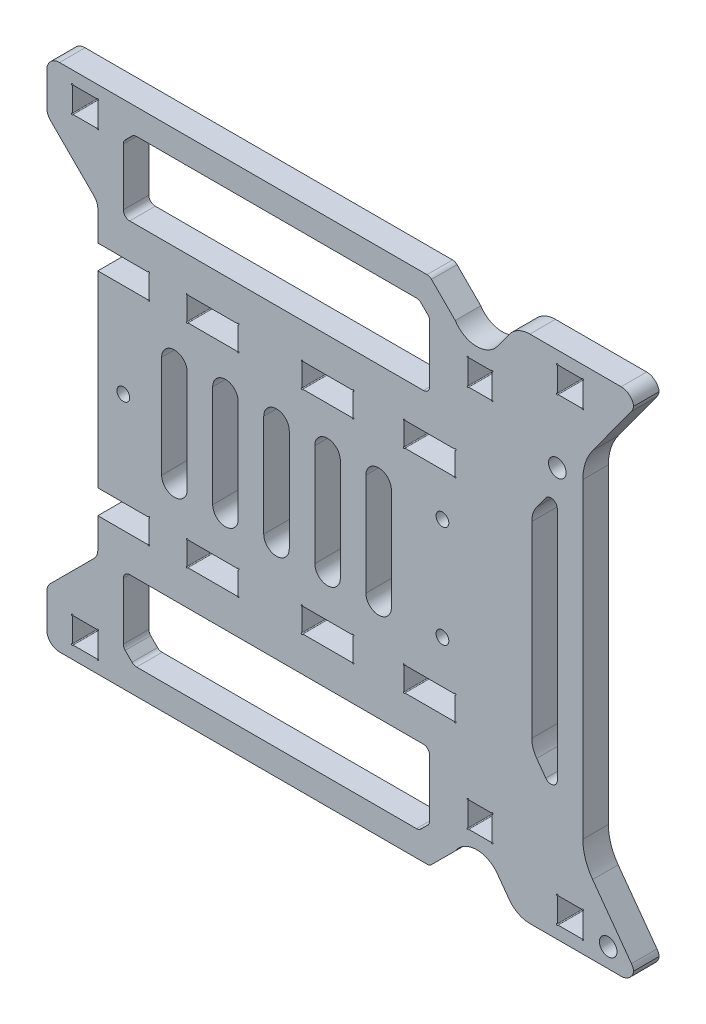
SolidWorks part; units mm, degrees
ref_plane "Front Plane" through (0, 0, 0) normal (0, 0, 1) x (1, 0, 0)
ref_plane "Top Plane" through (0, 0, 0) normal (0, 1, 0) x (1, 0, 0)
ref_plane "Right Plane" through (0, 0, 0) normal (1, 0, 0) x (0, 0, -1)
sketch "Sketch1" plane through (0, 0, 0) normal (0, 0, 1) x (1, 0, 0)
  line L0 (83.672, 0) -> (-43.8164, 0) construction
  line L1 (10.525, 38.1) -> (10.525, -38.1) construction
  line L2 (-27.575, 38.1) -> (48.625, 38.1)
  line L3 (99.425, -63.5) -> (99.425, -60.325)
  line L4 (99.425, -60.325) -> (74.025, -25.4)
  line L5 (-27.575, -63.5) -> (48.625, -63.5)
  line L6 (-27.575, 38.1) -> (-27.575, 54.5197)
  line L7 (48.625, 38.1) -> (48.625, 54.5197)
  line L8 (-24.9447, 57.15) -> (45.9947, 57.15)
  line L9 (-27.575, 63.5) -> (48.625, 63.5)
  line L10 (-33.925, 57.15) -> (-33.925, -57.15)
  line L11 (-27.575, 63.5) -> (-33.925, 57.15)
  line L12 (-24.9447, 57.15) -> (-27.575, 54.5197)
  line L13 (99.425, 63.5) -> (99.425, 60.325)
  line L14 (-23.0849, 59.0099) -> (-29.4349, 52.6599) construction
  line L15 (99.425, 60.325) -> (74.025, 25.4)
  line L16 (74.025, 25.4) -> (74.025, -25.4)
  line L17 (48.625, -38.1) -> (48.625, -54.5197)
  line L18 (-27.575, -38.1) -> (48.625, -38.1)
  line L19 (-24.9447, -57.15) -> (45.9947, -57.15)
  line L20 (-24.9447, -57.15) -> (-27.575, -54.5197)
  line L21 (-27.575, -38.1) -> (-27.575, -54.5197)
  line L22 (-27.575, -63.5) -> (-33.925, -57.15)
  line L23 (48.625, -63.5) -> (54.975, -57.15)
  line L24 (48.625, 63.5) -> (54.975, 57.15)
  line L25 (70.3271, -63.5) -> (99.425, -63.5)
  line L26 (45.9947, 57.15) -> (48.625, 54.5197)
  line L27 (45.9947, -57.15) -> (48.625, -54.5197)
  line L28 (70.3271, 63.5) -> (65.7089, 57.15)
  line L29 (70.3271, 63.5) -> (99.425, 63.5)
  line L30 (78.8831, 75.2646) -> (53.4831, 40.3396) construction
  line L31 (54.975, -42.3909) -> (54.975, -57.15)
  line L32 (70.3271, -63.5) -> (65.7089, -57.15)
  line L34 (48.625, -63.5) -> (54.975, -57.15)
  line L35 (65.7089, 57.15) -> (54.975, 42.3909)
  line L36 (54.975, 42.3909) -> (54.975, 57.15)
  line L37 (65.7089, -57.15) -> (54.975, -42.3909)
  point P7 (-27.575, 0)
  point P21 (74.025, 0)
  point P22 (-33.925, 0)
  dimension "D1" = 25.4
  dimension "D2" = 76.2
  dimension "D3" = 127
  dimension "D4" = 6.35
  dimension "D7" = 3.175
  dimension "D8" = 25.4
  dimension "D9" = 25.4
  dimension "D6" = 6.35
extrude "Boss-Extrude1" add sketch "Sketch1" along normal blind 6.35 contours L23 L32 L25 L3 L4 L16 L15 L13 L29 L28 L24 L9 L11 L10 L22 L5 L8 L26 L7 L2 L6 L12 L27 L19 L20 L21 L18 L17 region at (27.1557, 0, 0)
fillet "Fillet1" radius 6.35 4 edges at (70.3271, 63.5, 3.175) (70.3271, -63.5, 3.175) (54.975, -42.3909, 3.175) (54.975, 42.3909, 3.175)
fillet "Fillet3" radius 3.175 4 edges at (99.425, 63.5, 3.175) (99.425, 60.325, 3.175) (99.425, -60.325, 3.175) (99.425, -63.5, 3.175)
fillet "Fillet4" radius 6.35 2 edges at (74.025, -25.4, 3.175) (74.025, 25.4, 3.175)
fillet "Fillet7" radius 1.5875 4 edges at (-27.575, -38.1, 3.175) (48.625, -38.1, 3.175) (48.625, 38.1, 3.175) (-27.575, 38.1, 3.175)
fillet "Fillet8" radius 1.5875 2 edges at (48.625, -63.5, 3.175) (48.625, 63.5, 3.175)
fillet "Fillet9" radius 1.5875 8 edges at (-27.575, 54.5197, 3.175) (-24.9447, 57.15, 3.175) (-27.575, -54.5197, 3.175) (-24.9447, -57.15, 3.175) (45.9947, -57.15, 3.175) (48.625, -54.5197, 3.175) (48.625, 54.5197, 3.175) (45.9947, 57.15, 3.175)
sketch "Sketch2" plane through (0, 0, 6.35) normal (0, 0, 1) x (1, 0, 0)
  line L0 (-33.925, 0) -> (74.025, 0) construction
  line L1 (-33.925, 57.15) -> (-33.925, -57.15) construction
  line L2 (74.025, 23.3351) -> (74.025, -23.3351) construction
  line L3 (48.625, 39.6875) -> (48.625, 53.8622) construction
  line L4 (58.3484, 50.8) -> (63.9714, 50.8)
  line L5 (58.15, 50.6016) -> (58.15, 44.6484)
  line L6 (58.3484, 44.45) -> (63.9714, 44.45)
  line L7 (64.1698, 50.6016) -> (64.1698, 44.6484)
  line L8 (64.1698, -50.6016) -> (64.1698, -44.6484)
  line L9 (58.3484, -50.8) -> (63.9714, -50.8)
  line L10 (58.15, -50.6016) -> (58.15, -44.6484)
  line L11 (58.3484, -44.45) -> (63.9714, -44.45)
  arc A0 (58.3484, 50.8) -> (58.15, 50.6016) centre (58.15, 50.8) ccw
  arc A1 (64.1698, 50.6016) -> (63.9714, 50.8) centre (64.1698, 50.8) ccw
  arc A2 (63.9714, 44.45) -> (64.1698, 44.6484) centre (64.1698, 44.45) ccw
  arc A3 (58.15, 44.6484) -> (58.3484, 44.45) centre (58.15, 44.45) ccw
  arc A4 (63.9714, -44.45) -> (64.1698, -44.6484) centre (64.1698, -44.45) cw
  arc A5 (64.1698, -50.6016) -> (63.9714, -50.8) centre (64.1698, -50.8) cw
  arc A6 (58.3484, -50.8) -> (58.15, -50.6016) centre (58.15, -50.8) cw
  arc A7 (58.15, -44.6484) -> (58.3484, -44.45) centre (58.15, -44.45) cw
  point P10 (48.625, 46.7748)
  dimension "D5" = 0.3969
  dimension "D6" = 0.3969
  dimension "D7" = 0.3969
  dimension "D8" = 0.3969
  dimension "D1" = 6.0198
  dimension "D2" = 6.35
  dimension "D3" = 50.8
  dimension "D4" = 9.525
extrude "Cut-Extrude1" cut sketch "Sketch2" against normal through all
sketch "Sketch5" plane through (0, 0, 6.35) normal (0, 0, 1) x (1, 0, 0)
  line L0 (-33.925, 29.3675) -> (74.025, 29.3675) construction
  line L1 (-33.925, 57.15) -> (-33.925, -57.15) construction
  line L2 (74.025, 23.3351) -> (74.025, -23.3351) construction
  line L3 (-25.9875, 38.1) -> (47.0375, 38.1) construction
  line L4 (-33.925, 23.3731) -> (74.025, 23.3731) construction
  line L5 (-33.925, 0) -> (74.025, 0) construction
  line L6 (-11.5016, 29.3675) -> (0.8016, 29.3675)
  line L7 (-11.7, 29.169) -> (-11.7, 23.5715)
  line L8 (-11.5016, 23.3731) -> (0.8016, 23.3731)
  line L9 (1, 29.169) -> (1, 23.5715)
  line L10 (42.4734, 29.3675) -> (54.7766, 29.3675)
  line L11 (42.275, 29.169) -> (42.275, 23.5715)
  line L12 (42.4734, 23.3731) -> (54.7766, 23.3731)
  line L13 (54.975, 29.169) -> (54.975, 23.5715)
  line L14 (29.3766, 29.3675) -> (17.0734, 29.3675)
  line L15 (29.575, 29.169) -> (29.575, 23.5715)
  line L16 (29.3766, 23.3731) -> (17.0734, 23.3731)
  line L17 (16.875, 29.169) -> (16.875, 23.5715)
  line L18 (-21.4234, 29.3675) -> (-33.925, 29.3675)
  line L19 (-21.225, 29.169) -> (-21.225, 23.5715)
  line L20 (-21.4234, 23.3731) -> (-33.925, 23.3731)
  line L21 (-33.925, 29.3675) -> (-33.925, 23.3731)
  line L22 (-33.925, -29.3675) -> (-33.925, -23.3731)
  line L23 (-21.4234, -23.3731) -> (-33.925, -23.3731)
  line L24 (-21.225, -29.169) -> (-21.225, -23.5715)
  line L25 (-21.4234, -29.3675) -> (-33.925, -29.3675)
  line L26 (16.875, -29.169) -> (16.875, -23.5715)
  line L27 (29.3766, -23.3731) -> (17.0734, -23.3731)
  line L28 (29.575, -29.169) -> (29.575, -23.5715)
  line L29 (29.3766, -29.3675) -> (17.0734, -29.3675)
  line L30 (54.975, -29.169) -> (54.975, -23.5715)
  line L31 (42.4734, -23.3731) -> (54.7766, -23.3731)
  line L32 (42.275, -29.169) -> (42.275, -23.5715)
  line L33 (42.4734, -29.3675) -> (54.7766, -29.3675)
  line L34 (1, -29.169) -> (1, -23.5715)
  line L35 (-11.5016, -23.3731) -> (0.8016, -23.3731)
  line L36 (-11.7, -29.169) -> (-11.7, -23.5715)
  line L37 (-11.5016, -29.3675) -> (0.8016, -29.3675)
  line L38 (-33.925, 26.3703) -> (54.975, 26.3703) construction
  arc A0 (-21.225, 29.169) -> (-21.4234, 29.3675) centre (-21.225, 29.3675) ccw
  arc A1 (-11.5016, 29.3675) -> (-11.7, 29.169) centre (-11.7, 29.3675) ccw
  arc A2 (1, 29.169) -> (0.8016, 29.3675) centre (1, 29.3675) ccw
  arc A3 (29.575, 29.169) -> (29.3766, 29.3675) centre (29.575, 29.3675) ccw
  arc A4 (17.0734, 29.3675) -> (16.875, 29.169) centre (16.875, 29.3675) ccw
  arc A5 (54.975, 29.169) -> (54.7766, 29.3675) centre (54.975, 29.3675) ccw
  arc A6 (42.4734, 29.3675) -> (42.275, 29.169) centre (42.275, 29.3675) ccw
  arc A7 (17.0734, 23.3731) -> (16.875, 23.5715) centre (16.875, 23.3731) cw
  arc A8 (29.575, 23.5715) -> (29.3766, 23.3731) centre (29.575, 23.3731) cw
  arc A9 (42.4734, 23.3731) -> (42.275, 23.5715) centre (42.275, 23.3731) cw
  arc A10 (54.975, 23.5715) -> (54.7766, 23.3731) centre (54.975, 23.3731) cw
  arc A11 (1, 23.5715) -> (0.8016, 23.3731) centre (1, 23.3731) cw
  arc A12 (-11.5016, 23.3731) -> (-11.7, 23.5715) centre (-11.7, 23.3731) cw
  arc A13 (-21.225, 23.5715) -> (-21.4234, 23.3731) centre (-21.225, 23.3731) cw
  arc A14 (-21.225, -23.5715) -> (-21.4234, -23.3731) centre (-21.225, -23.3731) ccw
  arc A15 (-11.5016, -23.3731) -> (-11.7, -23.5715) centre (-11.7, -23.3731) ccw
  arc A16 (1, -23.5715) -> (0.8016, -23.3731) centre (1, -23.3731) ccw
  arc A17 (54.975, -23.5715) -> (54.7766, -23.3731) centre (54.975, -23.3731) ccw
  arc A18 (42.4734, -23.3731) -> (42.275, -23.5715) centre (42.275, -23.3731) ccw
  arc A19 (29.575, -23.5715) -> (29.3766, -23.3731) centre (29.575, -23.3731) ccw
  arc A20 (17.0734, -23.3731) -> (16.875, -23.5715) centre (16.875, -23.3731) ccw
  arc A21 (42.4734, -29.3675) -> (42.275, -29.169) centre (42.275, -29.3675) cw
  arc A22 (54.975, -29.169) -> (54.7766, -29.3675) centre (54.975, -29.3675) cw
  arc A23 (17.0734, -29.3675) -> (16.875, -29.169) centre (16.875, -29.3675) cw
  arc A24 (29.575, -29.169) -> (29.3766, -29.3675) centre (29.575, -29.3675) cw
  arc A25 (1, -29.169) -> (0.8016, -29.3675) centre (1, -29.3675) cw
  arc A26 (-11.5016, -29.3675) -> (-11.7, -29.169) centre (-11.7, -29.3675) cw
  arc A27 (-21.225, -29.169) -> (-21.4234, -29.3675) centre (-21.225, -29.3675) cw
  dimension "D11" = 0.3969
  dimension "D12" = 0.3969
  dimension "D13" = 0.3969
  dimension "D14" = 0.3969
  dimension "D15" = 0.3969
  dimension "D16" = 0.3969
  dimension "D17" = 0.3969
  dimension "D1" = 8.7325
  dimension "D3" = 12.7
  dimension "D4" = 12.7
  dimension "D5" = 41.275
  dimension "D6" = 34.925
  dimension "D7" = 12.7
  dimension "D8" = 12.7
  dimension "D9" = 50.8
  dimension "D10" = 0
  dimension "D2" = 5.9944
extrude "Cut-Extrude4" cut sketch "Sketch5" against normal through all
sketch "Sketch6" plane through (0, 0, 6.35) normal (0, 0, 1) x (1, 0, 0)
  line L0 (80.375, 34.1312) -> (80.375, -34.1312)
  line L1 (98.8177, 59.49) -> (75.2395, 27.07) construction
  line L2 (98.8177, -59.49) -> (75.2395, -27.07) construction
  line L3 (74.025, 23.3351) -> (74.025, -23.3351) construction
  line L4 (86.725, 34.1312) -> (86.725, -34.1312)
  line L5 (86.725, 34.1312) -> (86.725, 42.8625)
  line L6 (86.725, 42.8625) -> (80.375, 34.1312)
  line L7 (86.725, -34.1312) -> (86.725, -42.8625)
  line L8 (86.725, -42.8625) -> (80.375, -34.1312)
  dimension "D1" = 6.35
  dimension "D2" = 6.35
extrude "Boss-Extrude2" add sketch "Sketch6" against normal blind 6.35
fillet "Fillet10" radius 1.5875 2 edges at (80.375, -34.1312, 3.175) (80.375, 34.1312, 3.175)
fillet "Fillet11" radius 12.7 2 edges at (86.725, 42.8625, 3.175) (86.725, -42.8625, 3.175)
hole_wizard "11/64 (0.17188) Diameter Hole1" positions "Sketch8" profile "Sketch7" hole size "11/64" standard "ANSI Inch" end condition through all
sketch "Sketch8" plane through (0, 0, 6.35) normal (0, 0, 1) x (1, 0, 0)
  line L1 (-33.925, -29.3675) -> (-33.925, -57.15) construction
  line L2 (73.5606, 63.5) -> (96.25, 63.5) construction
  point P0 (80.375, 38.1)
  dimension "D1" = 25.4
  dimension "D2" = 114.3
sketch "Sketch7" plane through (80.375, 38.1, 6.35) normal (1, 0, 0) x (0, -1, 0)
  line L0 (0, 0) -> (0, 6.35)
  line L1 (0, 6.35) -> (2.1829, 6.35)
  line L2 (2.1829, 6.35) -> (2.1829, 0)
  line L5 (2.1829, 0) -> (0, 0)
  line L11 (0, -6.35) -> (0, 107.95) construction
  dimension "Thru Hole Dia." = 4.3658
  dimension "Thru Hole Depth" = 6.35
sketch "Sketch10" plane through (0, 0, 6.35) normal (0, 0, 1) x (1, 0, 0)
  line L0 (51.8, 63.5) -> (51.8, -63.5) construction
  line L1 (-27.575, 63.5) -> (47.9674, 63.5) construction
  line L2 (-27.575, -63.5) -> (47.9674, -63.5) construction
  line L3 (23.225, 29.3675) -> (23.225, -29.3675) construction
  line L4 (29.3766, 29.3675) -> (17.0734, 29.3675) construction
  line L5 (17.0734, -29.3675) -> (29.3766, -29.3675) construction
  line L6 (-27.575, 63.5) -> (-27.575, -63.5) construction
  line L7 (-33.925, 0) -> (74.025, 0) construction
  line L8 (-33.925, 23.3731) -> (-33.925, -23.3731) construction
  line L9 (74.025, 23.3351) -> (74.025, -23.3351) construction
  circle A0 centre (51.8, 12.7) radius 1.5875
  circle A1 centre (51.8, -12.7) radius 1.5875
  circle A2 centre (-27.575, 0) radius 1.5875
  dimension "D3" = 3.175
  dimension "D5" = 79.375
  dimension "D1" = 28.575
  dimension "D2" = 79.375
  dimension "D4" = 12.7
extrude "Cut-Extrude6" cut sketch "Sketch10" against normal through all
sketch "Sketch11" plane through (0, 0, 6.35) normal (0, 0, 1) x (1, 0, 0)
  line L0 (-62.0481, -60.325) -> (124.8486, -60.325) construction
  line L1 (-27.575, -63.5) -> (47.9674, -63.5) construction
  line L2 (-27.575, -63.5) -> (-33.925, -57.15)
  line L3 (-33.925, -57.15) -> (-33.925, -50.8)
  line L4 (-33.925, -50.8) -> (-33.925, -38.1)
  line L5 (-46.625, -50.8) -> (-46.625, -63.5)
  line L6 (-46.625, -63.5) -> (-27.575, -63.5)
  line L7 (-46.625, -50.8) -> (-33.925, -38.1)
  line L8 (-33.925, -29.3675) -> (-33.925, -57.15) construction
  line L9 (-46.625, 63.5) -> (-27.575, 63.5)
  line L10 (-33.925, 0) -> (74.025, 0) construction
  line L11 (-46.625, 50.8) -> (-46.625, 63.5)
  line L12 (-33.925, 23.3731) -> (-33.925, -23.3731) construction
  line L13 (74.025, 23.3351) -> (74.025, -23.3351) construction
  line L14 (-46.625, 50.8) -> (-33.925, 38.1)
  line L15 (-33.925, 57.15) -> (-33.925, 50.8)
  line L16 (-27.575, 63.5) -> (-33.925, 57.15)
  line L17 (-33.925, 50.8) -> (-33.925, 38.1)
  point P2 (10.1962, -63.5)
  dimension "D1" = 3.175
  dimension "D2" = 12.7
  dimension "D3" = 12.7
extrude "Boss-Extrude4" add sketch "Sketch11" against normal blind 6.35
sketch "Sketch12" plane through (0, 0, 6.35) normal (0, 0, 1) x (1, 0, 0)
  line L0 (73.5606, -63.5) -> (96.25, -63.5) construction
  line L1 (86.5266, -60.325) -> (80.5734, -60.325)
  line L2 (86.725, -60.1266) -> (86.725, -54.1734)
  line L3 (86.5266, -53.975) -> (80.5734, -53.975)
  line L4 (80.375, -60.1266) -> (80.375, -54.1734)
  line L5 (-33.925, -29.3675) -> (-33.925, -38.1) construction
  line L6 (-33.925, 0) -> (74.025, 0) construction
  line L7 (86.725, 60.1266) -> (86.725, 54.1734)
  line L8 (86.5266, 60.325) -> (80.5734, 60.325)
  line L9 (80.375, 60.1266) -> (80.375, 54.1734)
  line L10 (86.5266, 53.975) -> (80.5734, 53.975)
  line L11 (83.55, -60.325) -> (-33.7266, -60.325) construction
  line L12 (-34.1234, -60.325) -> (-54.5439, -60.325) construction
  line L13 (-34.1234, -60.325) -> (-40.0766, -60.325)
  line L14 (-33.925, -60.1266) -> (-33.925, -54.1734)
  line L15 (-34.1234, -53.975) -> (-40.0766, -53.975)
  line L16 (-40.275, -60.1266) -> (-40.275, -54.1734)
  line L17 (-34.1234, 60.325) -> (-40.0766, 60.325)
  line L18 (-33.925, 60.1266) -> (-33.925, 54.1734)
  line L19 (-40.275, 60.1266) -> (-40.275, 54.1734)
  line L20 (-34.1234, 53.975) -> (-40.0766, 53.975)
  arc A0 (-40.275, 60.1266) -> (-40.0766, 60.325) centre (-40.275, 60.325) cw
  arc A1 (80.5734, -53.975) -> (80.375, -54.1734) centre (80.375, -53.975) ccw
  arc A2 (86.725, -54.1734) -> (86.5266, -53.975) centre (86.725, -53.975) ccw
  arc A3 (80.375, -60.1266) -> (80.5734, -60.325) centre (80.375, -60.325) ccw
  arc A4 (86.5266, -60.325) -> (86.725, -60.1266) centre (86.725, -60.325) ccw
  arc A5 (86.5266, 60.325) -> (86.725, 60.1266) centre (86.725, 60.325) cw
  arc A6 (80.375, 60.1266) -> (80.5734, 60.325) centre (80.375, 60.325) cw
  arc A7 (80.5734, 53.975) -> (80.375, 54.1734) centre (80.375, 53.975) cw
  arc A8 (86.725, 54.1734) -> (86.5266, 53.975) centre (86.725, 53.975) cw
  arc A9 (-40.0766, -53.975) -> (-40.275, -54.1734) centre (-40.275, -53.975) ccw
  arc A10 (-33.925, -54.1734) -> (-34.1234, -53.975) centre (-33.925, -53.975) ccw
  arc A11 (-34.1234, -60.325) -> (-33.925, -60.1266) centre (-33.925, -60.325) ccw
  arc A12 (-40.275, -60.1266) -> (-40.0766, -60.325) centre (-40.275, -60.325) ccw
  arc A13 (-34.1234, 60.325) -> (-33.925, 60.1266) centre (-33.925, 60.325) cw
  arc A14 (-33.925, 54.1734) -> (-34.1234, 53.975) centre (-33.925, 53.975) cw
  arc A15 (-40.0766, 53.975) -> (-40.275, 54.1734) centre (-40.275, 53.975) cw
  point P4 (84.9053, -63.5)
  dimension "D5" = 0.3969
  dimension "D6" = 0.3969
  dimension "D7" = 0.3969
  dimension "D8" = 0.3969
  dimension "D12" = 0.3969
  dimension "D13" = 0.3969
  dimension "D14" = 0.3969
  dimension "D15" = 0.3969
  dimension "D1" = 6.35
  dimension "D2" = 6.35
  dimension "D3" = 3.175
  dimension "D4" = 114.3
  dimension "D9" = 6.35
  dimension "D10" = 6.35
  dimension "D11" = 120.65
extrude "Cut-Extrude7" cut sketch "Sketch12" against normal blind 6.35
fillet "Fillet12" radius 3.175 6 edges at (-46.625, 63.5, 3.175) (-46.625, 50.8, 3.175) (-33.925, 38.1, 3.175) (-46.625, -63.5, 3.175) (-46.625, -50.8, 3.175) (-33.925, -38.1, 3.175)
hole_wizard "11/64 (0.17188) Diameter Hole2" positions "Sketch14" profile "Sketch13" hole size "11/64" standard "ANSI Inch" end condition through all
sketch "Sketch14" plane through (0, 0, 0) normal (0, 0, -1) x (-1, 0, 0)
  line L0 (-73.5606, -63.5) -> (-96.25, -63.5) construction
  point P0 (-93.0328, -58.7375)
  dimension "D1" = 4.7625
  dimension "D2" = 6.35
sketch "Sketch13" plane through (93.0328, -58.7375, 0) normal (1, 0, 0) x (0, 1, 0)
  line L0 (0, 0) -> (0, 6.35)
  line L1 (0, 6.35) -> (2.1829, 6.35)
  line L2 (2.1829, 6.35) -> (2.1829, 0)
  line L5 (2.1829, 0) -> (0, 0)
  line L11 (0, -6.35) -> (0, 107.95) construction
  dimension "Thru Hole Dia." = 4.3658
  dimension "Thru Hole Depth" = 6.35
sketch "Sketch15" plane through (0, 0, 6.35) normal (0, 0, 1) x (1, 0, 0)
  line L0 (-33.925, 0) -> (86.725, 0) construction
  line L1 (-33.925, 23.3731) -> (-33.925, -23.3731) construction
  line L2 (86.725, -38.7327) -> (86.725, 38.7327) construction
  line L3 (-14.875, -12.7) -> (-14.875, 12.7) construction
  line L4 (-18.05, -12.7) -> (-18.05, 12.7)
  line L5 (-11.7, -12.7) -> (-11.7, 12.7)
  line L6 (-2.175, -12.7) -> (-2.175, 12.7) construction
  line L7 (-5.35, -12.7) -> (-5.35, 12.7)
  line L8 (1, -12.7) -> (1, 12.7)
  line L9 (10.525, -12.7) -> (10.525, 12.7) construction
  line L10 (7.35, -12.7) -> (7.35, 12.7)
  line L11 (13.7, -12.7) -> (13.7, 12.7)
  line L12 (23.225, -12.7) -> (23.225, 12.7) construction
  line L13 (20.05, -12.7) -> (20.05, 12.7)
  line L14 (26.4, -12.7) -> (26.4, 12.7)
  line L15 (35.925, -12.7) -> (35.925, 12.7) construction
  line L16 (32.75, -12.7) -> (32.75, 12.7)
  line L17 (39.1, -12.7) -> (39.1, 12.7)
  arc A0 (-18.05, -12.7) -> (-11.7, -12.7) centre (-14.875, -12.7) ccw
  arc A1 (-11.7, 12.7) -> (-18.05, 12.7) centre (-14.875, 12.7) ccw
  arc A2 (-5.35, -12.7) -> (1, -12.7) centre (-2.175, -12.7) ccw
  arc A3 (1, 12.7) -> (-5.35, 12.7) centre (-2.175, 12.7) ccw
  arc A4 (7.35, -12.7) -> (13.7, -12.7) centre (10.525, -12.7) ccw
  arc A5 (13.7, 12.7) -> (7.35, 12.7) centre (10.525, 12.7) ccw
  arc A6 (20.05, -12.7) -> (26.4, -12.7) centre (23.225, -12.7) ccw
  arc A7 (26.4, 12.7) -> (20.05, 12.7) centre (23.225, 12.7) ccw
  arc A8 (32.75, -12.7) -> (39.1, -12.7) centre (35.925, -12.7) ccw
  arc A9 (39.1, 12.7) -> (32.75, 12.7) centre (35.925, 12.7) ccw
  point P8 (-14.875, 0)
  point P17 (-2.175, 0)
  point P24 (10.525, 0)
  point P31 (23.225, 0)
  point P38 (35.925, 0)
  dimension "D1" = 19.05
  dimension "D2" = 5
extrude "Cut-Extrude8" cut sketch "Sketch15" against normal through all
